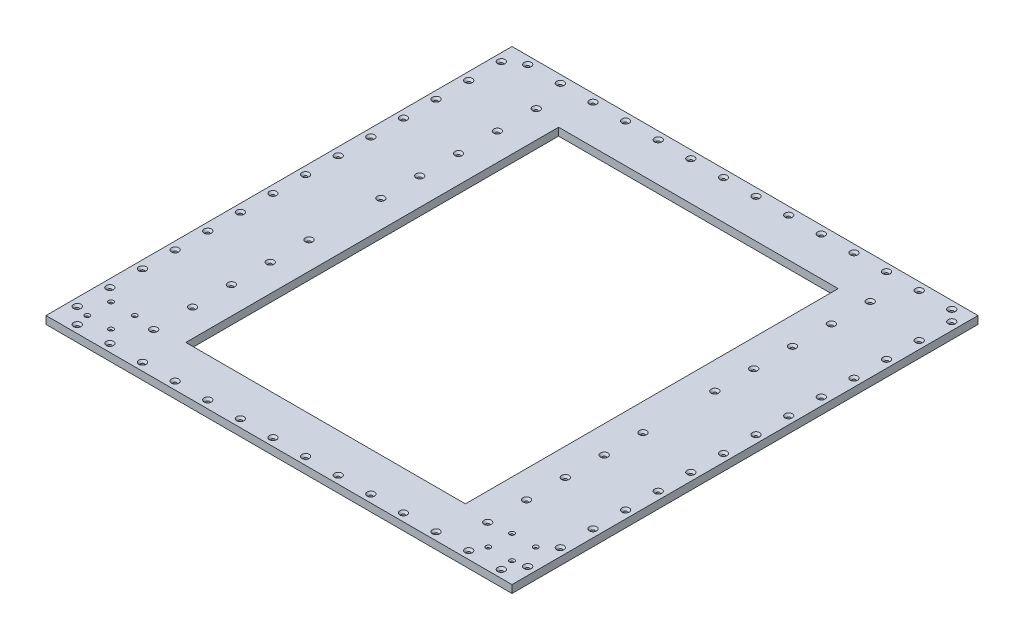
SolidWorks part; units mm, degrees
ref_plane "Płaszczyzna przednia" through (0, 0, 0) normal (0, 0, 1) x (1, 0, 0)
ref_plane "Płaszczyzna górna" through (0, 0, 0) normal (0, 1, 0) x (1, 0, 0)
ref_plane "Płaszczyzna prawa" through (0, 0, 0) normal (1, 0, 0) x (0, 0, -1)
sketch "Sketch1" plane through (0, 0, 0) normal (0, 1, 0) x (1, 0, 0)
  line L1 (0, 0) -> (600, 0)
  line L2 (0, 0) -> (0, 600)
  line L3 (0, 600) -> (600, 600)
  line L4 (600, 0) -> (600, 600)
  line L5 (0, 0) -> (600, 600) construction
  line L6 (0, 600) -> (600, 0) construction
  point P4 (300, 300)
  dimension "D1" = 600
  dimension "D2" = 600
extrude "Boss-Extrude1" add sketch "Sketch1" along normal blind 10
hole_wizard "CSK for M4 Flat Head Machine Screw1" positions "Sketch2" profile "Sketch3" countersink size "M4" standard "ANSI Metric" end condition through all
sketch "Sketch2" plane through (0, 10, 0) normal (0, 1, 0) x (1, 0, 0)
  line L0 (0, 0) -> (600, 0) construction
  line L1 (0, 600) -> (0, 0) construction
  line L2 (600, 0) -> (600, 600) construction
  point P0 (30.25, 10)
  point P14 (72.25, 10)
  point P15 (114.25, 10)
  point P16 (156.25, 10)
  point P17 (198.25, 10)
  point P18 (240.25, 10)
  point P19 (282.25, 10)
  point P20 (324.25, 10)
  point P21 (366.25, 10)
  point P22 (408.25, 10)
  point P23 (450.25, 10)
  point P24 (492.25, 10)
  point P25 (534.25, 10)
  point P26 (576.25, 10)
  point P27 (72.25, 590)
  point P28 (114.25, 590)
  point P29 (156.25, 590)
  point P30 (198.25, 590)
  point P31 (240.25, 590)
  point P32 (282.25, 590)
  point P33 (324.25, 590)
  point P34 (366.25, 590)
  point P35 (408.25, 590)
  point P36 (450.25, 590)
  point P37 (492.25, 590)
  point P38 (534.25, 590)
  point P39 (576.25, 590)
  point P40 (30.25, 590)
  point P42 (590, 30.25)
  point P59 (10, 30.25)
  point P60 (10, 72.25)
  point P61 (10, 114.25)
  point P62 (10, 156.25)
  point P63 (10, 198.25)
  point P64 (10, 240.25)
  point P65 (10, 282.25)
  point P66 (10, 324.25)
  point P67 (10, 366.25)
  point P68 (10, 408.25)
  point P69 (10, 450.25)
  point P70 (10, 492.25)
  point P71 (10, 534.25)
  point P72 (10, 576.25)
  point P73 (590, 72.25)
  point P74 (590, 114.25)
  point P75 (590, 156.25)
  point P76 (590, 198.25)
  point P77 (590, 240.25)
  point P78 (590, 282.25)
  point P79 (590, 324.25)
  point P80 (590, 366.25)
  point P81 (590, 408.25)
  point P82 (590, 450.25)
  point P83 (590, 492.25)
  point P84 (590, 534.25)
  point P85 (590, 576.25)
  dimension "D1" = 10
  dimension "D2" = 30.25
  dimension "D5" = 10
  dimension "D6" = 30.25
  dimension "D3" = 14
  dimension "D4" = 2
  dimension "D7" = 2
  dimension "D8" = 14
sketch "Sketch3" plane through (30.25, 10, -10) normal (1, 0, 0) x (0, 0, 1)
  line L0 (0, 0) -> (0, 10)
  line L1 (0, 10) -> (2.15, 10)
  line L2 (2.15, 10) -> (2.15, 2.55)
  line L3 (2.15, 2.55) -> (4.7, 0)
  line L5 (4.7, 0) -> (0, 0)
  line L6 (-2.15, 2.55) -> (-4.7, 0) construction
  line L11 (0, -6.35) -> (0, 107.95) construction
  dimension "Thru Hole Dia." = 4.3
  dimension "Thru Hole Depth" = 10
  dimension "Near C'Sink Dia." = 9.4
  dimension "Near C'Sink Angle" = 90
hole_wizard "CSK for M4 Flat Head Machine Screw2" positions "Sketch4" profile "Sketch5" countersink size "M4" standard "ANSI Metric" end condition through all
sketch "Sketch4" plane through (0, 10, 0) normal (0, 1, 0) x (1, 0, 0)
  line L0 (0, 0) -> (600, 0) construction
  line L1 (0, 600) -> (0, 0) construction
  line L2 (600, 600) -> (0, 600) construction
  point P0 (84.93, 53.75)
  point P14 (514.93, 53.75)
  point P15 (514.93, 103.75)
  point P16 (514.93, 153.75)
  point P17 (514.93, 203.75)
  point P18 (514.93, 253.75)
  point P19 (84.93, 103.75)
  point P20 (84.93, 153.75)
  point P21 (84.93, 203.75)
  point P22 (84.93, 253.75)
  point P23 (84.93, 546.25)
  point P36 (514.93, 546.25)
  point P37 (514.93, 496.25)
  point P38 (514.93, 446.25)
  point P39 (514.93, 396.25)
  point P40 (514.93, 346.25)
  point P41 (84.93, 496.25)
  point P42 (84.93, 446.25)
  point P43 (84.93, 396.25)
  point P44 (84.93, 346.25)
  dimension "D1" = 53.75
  dimension "D2" = 84.93
  dimension "D5" = 53.75
  dimension "D6" = 84.93
  dimension "D3" = 2
  dimension "D4" = 5
  dimension "D7" = 2
  dimension "D8" = 5
sketch "Sketch5" plane through (84.93, 10, -53.75) normal (1, 0, 0) x (0, 0, 1)
  line L0 (0, 0) -> (0, 10)
  line L1 (0, 10) -> (2.15, 10)
  line L2 (2.15, 10) -> (2.15, 2.55)
  line L3 (2.15, 2.55) -> (4.7, 0)
  line L5 (4.7, 0) -> (0, 0)
  line L6 (-2.15, 2.55) -> (-4.7, 0) construction
  line L11 (0, -6.35) -> (0, 107.95) construction
  dimension "Thru Hole Dia." = 4.3
  dimension "Thru Hole Depth" = 10
  dimension "Near C'Sink Dia." = 9.4
  dimension "Near C'Sink Angle" = 90
sketch "Sketch6" plane through (0, 10, 0) normal (0, 1, 0) x (1, 0, 0)
  line L0 (0, 600) -> (0, 0) construction
  line L1 (120, 540) -> (480, 540)
  line L2 (120, 540) -> (120, 60)
  line L3 (120, 60) -> (480, 60)
  line L4 (480, 540) -> (480, 60)
  line L5 (120, 540) -> (480, 60) construction
  line L6 (120, 60) -> (480, 540) construction
  line L7 (600, 0) -> (600, 600) construction
  line L8 (0, 0) -> (600, 0) construction
  line L9 (600, 600) -> (0, 600) construction
  point P4 (300, 300)
  dimension "D1" = 120
  dimension "D2" = 120
  dimension "D3" = 60
  dimension "D4" = 60
extrude "Cut-Extrude1" cut sketch "Sketch6" against normal blind 10
sketch "Sketch7" plane through (0, 0, 0) normal (0, -1, 0) x (1, 0, 0)
  line L0 (600, -600) -> (0, -600) construction
  line L1 (72, -535) -> (58, -535)
  line L2 (72, -535) -> (72, -65)
  line L3 (72, -65) -> (58, -65)
  line L4 (58, -535) -> (58, -65)
  line L5 (72, -535) -> (58, -65) construction
  line L6 (72, -65) -> (58, -535) construction
  line L7 (0, -600) -> (0, 0) construction
  line L8 (112, -535) -> (112, -65)
  line L9 (112, -535) -> (98, -535)
  line L10 (98, -535) -> (98, -65)
  line L11 (112, -65) -> (98, -65)
  line L12 (542, -535) -> (542, -65)
  line L13 (542, -65) -> (528, -65)
  line L14 (528, -535) -> (528, -65)
  line L15 (542, -535) -> (528, -535)
  line L16 (502, -65) -> (488, -535) construction
  line L17 (502, -535) -> (502, -65)
  line L18 (502, -535) -> (488, -535)
  line L19 (488, -535) -> (488, -65)
  line L20 (502, -65) -> (488, -65)
  point P4 (65, -300)
  dimension "D1" = 65
  dimension "D2" = 470
  dimension "D3" = 14
  dimension "D4" = 72
  dimension "D5" = 2
  dimension "D6" = 2
extrude "Cut-Extrude2" cut sketch "Sketch7" against normal blind 2
chamfer "Chamfer1" distance 2 angle 45 16 edges at (65, 2, -535) (58, 2, -300) (65, 2, -65) (72, 2, -300) (98, 2, -300) (105, 2, -65) (112, 2, -300) (105, 2, -535) (488, 2, -300) (495, 2, -65) (502, 2, -300) (495, 2, -535) (528, 2, -300) (535, 2, -65) (542, 2, -300) (535, 2, -535)
sketch "Sketch8" plane through (0, 0, 0) normal (0, -1, 0) x (1, 0, 0)
  line L0 (600, 0) -> (600, -600) construction
  line L1 (20, -600) -> (580, -600) construction
  circle A0 centre (558, -558) radius 8
  dimension "D1" = 16
  dimension "D2" = 42
  dimension "D3" = 42
extrude "Cut-Extrude3" cut sketch "Sketch8" against normal blind 5
hole_wizard "CSK for M3 Flat Head Machine Screw1" positions "Sketch9" profile "Sketch10" countersink size "M3" standard "ANSI Metric" end condition through all
sketch "Sketch9" plane through (0, 10, 0) normal (0, 1, 0) x (1, 0, 0)
  line L0 (600, 0) -> (600, 600) construction
  line L1 (0, 0) -> (600, 0) construction
  line L7 (300, 0) -> (300, 600) construction
  line L8 (600, 600) -> (0, 600) construction
  point P0 (542.9, 57.1)
  point P2 (573.4, 57.1)
  point P4 (573.4, 26.6)
  point P6 (542.9, 26.6)
  point P35 (57.1, 26.6)
  point P36 (26.6, 26.6)
  point P37 (26.6, 57.1)
  point P38 (57.1, 57.1)
  dimension "D1" = 57.1
  dimension "D2" = 26.6
  dimension "D3" = 30.5
  dimension "D4" = 30.5
  dimension "D5" = 600
  dimension "D6" = 300
sketch "Sketch10" plane through (542.9, 10, -57.1) normal (1, 0, 0) x (0, 0, 1)
  line L0 (0, 0) -> (0, 10)
  line L1 (0, 10) -> (1.6, 10)
  line L2 (1.6, 10) -> (1.6, 1.55)
  line L3 (1.6, 1.55) -> (3.15, 0)
  line L5 (3.15, 0) -> (0, 0)
  line L6 (-1.6, 1.55) -> (-3.15, 0) construction
  line L11 (0, -6.35) -> (0, 107.95) construction
  dimension "Thru Hole Dia." = 3.2
  dimension "Thru Hole Depth" = 10
  dimension "Near C'Sink Dia." = 6.3
  dimension "Near C'Sink Angle" = 90
sketch "Sketch11" plane through (0, 0, 0) normal (0, -1, 0) x (1, 0, 0)
  line L0 (0, -600) -> (0, 0) construction
  line L1 (600, -600) -> (0, -600) construction
  circle A0 centre (42, -558) radius 8
  dimension "D1" = 16
  dimension "D2" = 42
  dimension "D3" = 42
extrude "Cut-Extrude4" cut sketch "Sketch11" against normal blind 5
sketch "Sketch12" plane through (0, 0, 0) normal (0, -1, 0) x (1, 0, 0)
  line L0 (600, -600) -> (0, -600) construction
  line L1 (600, 0) -> (600, -600) construction
  circle A0 centre (425, -558) radius 4
  dimension "D1" = 42
  dimension "D2" = 8
  dimension "D3" = 175
extrude "Cut-Extrude5" cut sketch "Sketch12" against normal blind 5
sketch "Sketch13" plane through (0, 0, 0) normal (0, -1, 0) x (-1, 0, 0)
  line L0 (-600, 600) -> (0, 600) construction
  line L1 (0, 20) -> (0, 580) construction
  circle A0 centre (-175, 558) radius 4
  dimension "D1" = 42
  dimension "D2" = 175
  dimension "D3" = 8
extrude "Cut-Extrude6" cut sketch "Sketch13" against normal blind 5
sketch "Sketch14" plane through (0, -560, 0) normal (0, 1, 0) x (1, 0, 0)
  line L0 (0, 600) -> (600, 600) construction
  line L1 (0, 0) -> (0, 600) construction
  circle A0 centre (175, 558) radius 4
  dimension "D1" = 42
  dimension "D2" = 175
  dimension "D3" = 8
